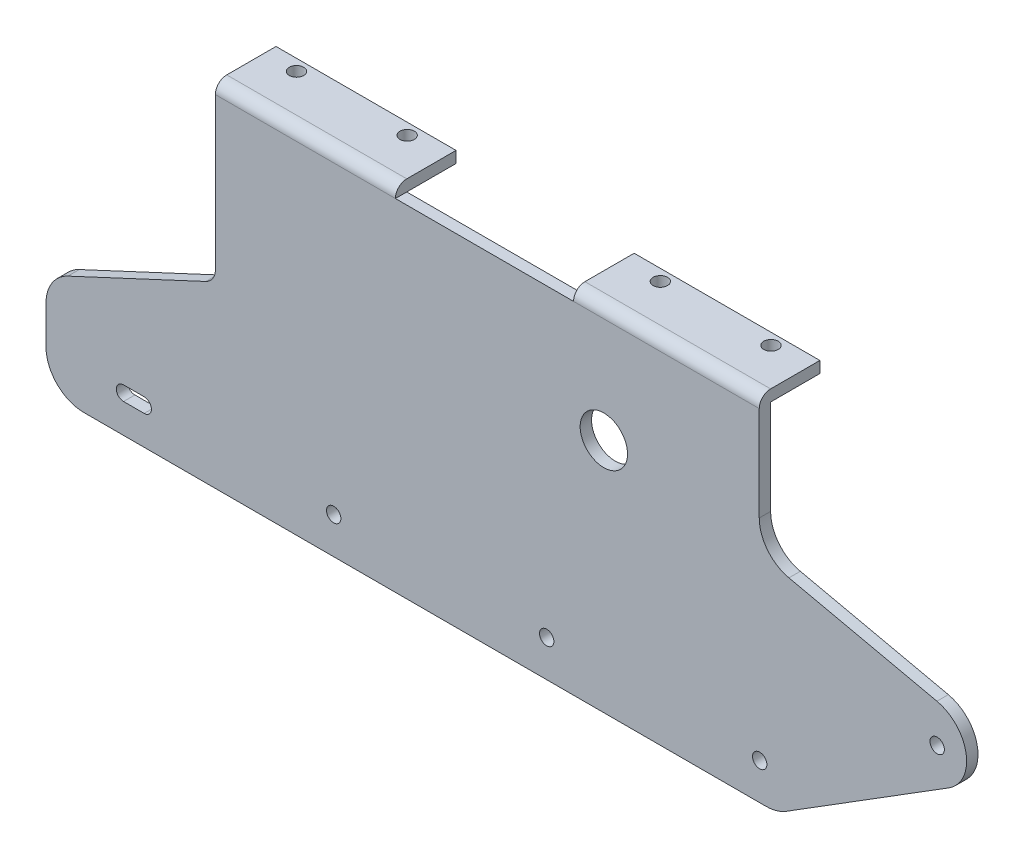
SolidWorks part; units mm, degrees
material "1060 Alloy"
ref_plane "Front Plane" through (0, 0, 0) normal (0, 0, 1) x (1, 0, 0)
ref_plane "Top Plane" through (0, 0, 0) normal (0, 1, 0) x (1, 0, 0)
ref_plane "Right Plane" through (0, 0, 0) normal (1, 0, 0) x (0, 0, -1)
sketch "Sketch1" plane through (0, 0, 0) normal (0, 0, 1) x (1, 0, 0)
  line L0 (0, 0) -> (143.5, 0)
  line L1 (143.5, 0) -> (143.5, -25)
  line L2 (151.3356, -34.763) -> (190.3874, -43.4205)
  line L3 (193.5222, -61.664) -> (150.6069, -88.4805)
  line L4 (145.3077, -90) -> (-34.6923, -90)
  line L5 (-44.6923, -80) -> (-44.6923, -70)
  line L6 (-38.9185, -60.9369) -> (-2.5276, -43.9676)
  line L7 (0, 0) -> (0, -40)
  arc A0 (-44.6923, -70) -> (-38.9185, -60.9369) centre (-34.6923, -70) cw
  arc A1 (143.5, -25) -> (151.3356, -34.763) centre (153.5, -25) ccw
  arc A2 (190.3874, -43.4205) -> (193.5222, -61.664) centre (188.223, -53.1835) cw
  arc A3 (145.3077, -90) -> (150.6069, -88.4805) centre (145.3077, -80) ccw
  arc A4 (-44.6923, -80) -> (-34.6923, -90) centre (-34.6923, -80) ccw
  arc A5 (-2.5276, -43.9676) -> (0, -40) centre (-4.3777, -40) ccw
  dimension "D6" = 10
  dimension "D7" = 10
  dimension "D10" = 10
  dimension "D11" = 40
  dimension "D12" = 10
  dimension "D15" = 10
  dimension "D1" = 143.5
  dimension "D2" = 25
  dimension "D3" = 40
  dimension "D4" = 90
  dimension "D5" = 12.5
  dimension "D8" = 180
  dimension "D9" = 32
  dimension "D13" = 10
  dimension "D14" = 25
extrude "Boss-Extrude1" add sketch "Sketch1" along normal blind 3
sketch "Sketch2" plane through (0, 0, 3) normal (0, 0, 1) x (1, 0, 0)
  line L0 (190.448, -53.5027) -> (198.218, -53.5027) construction
  line L1 (190.448, -53.5027) -> (190.3874, -43.4205) construction
  line L2 (190.448, -53.5027) -> (190.448, -63.585) construction
  line L3 (150.6069, -88.4805) -> (193.5222, -61.664) construction
  line L4 (143.6184, -80.35) -> (143.6184, -90) construction
  line L5 (-34.6923, -90) -> (145.3077, -90) construction
  line L6 (143.6184, -80.35) -> (163.6184, -80.35) construction
  line L7 (143.6184, -80.35) -> (87.4184, -80.35) construction
  line L8 (87.4184, -80.35) -> (31.2184, -80.35) construction
  line L9 (31.2184, -80.35) -> (-18.7816, -80.35) construction
  line L10 (-18.7816, -80.35) -> (-24.2316, -80.35) construction
  line L11 (-18.7816, -82.25) -> (-24.2316, -82.25)
  line L12 (-18.7816, -78.45) -> (-24.2316, -78.45)
  line L13 (102.5, -27.75) -> (0, -27.75) construction
  line L14 (0, 0) -> (0, -40) construction
  line L15 (143.5, 0) -> (0, 0) construction
  circle A0 centre (190.448, -53.5027) radius 1.9
  arc A1 (193.5222, -61.664) -> (190.3874, -43.4205) centre (188.223, -53.1835) ccw construction
  circle A2 centre (143.6184, -80.35) radius 1.9
  circle A3 centre (87.4184, -80.35) radius 1.9
  circle A4 centre (31.2184, -80.35) radius 1.9
  arc A5 (-18.7816, -82.25) -> (-18.7816, -78.45) centre (-18.7816, -80.35) ccw
  arc A6 (-24.2316, -78.45) -> (-24.2316, -82.25) centre (-24.2316, -80.35) ccw
  circle A7 centre (102.5, -27.75) radius 6.25
  point P22 (-21.5066, -80.35)
  dimension "D1" = 3.8
  dimension "D7" = 1.9
  dimension "D8" = 5.45
  dimension "D11" = 12.5
  dimension "D2" = 7.77
  dimension "D3" = 9.65
  dimension "D4" = 20
  dimension "D5" = 56.2
  dimension "D6" = 50
  dimension "D9" = 102.5
  dimension "D10" = 27.75
extrude "Cut-Extrude1" cut sketch "Sketch2" against normal through all contours A7 | A2 | A0 | A3 | A4 | L12 A6 L11 A5
sketch "Sketch3" plane through (143.5, 0, 0) normal (1, 0, 0) x (0, 0, -1)
  line L0 (0, 0) -> (13, 0)
  line L1 (0, 3) -> (13, 3)
  line L2 (13, 3) -> (13, 0)
  line L3 (-3, 0) -> (0, 0)
  line L4 (-3, -25) -> (-3, 0) construction
  line L5 (-3, -25) -> (-3, 0)
  line L6 (0, -25) -> (0, 0) construction
  line L7 (0, -25) -> (0, 0)
  arc A0 (0, 3) -> (-3, 0) centre (0, 0) ccw
  dimension "D1" = 3
  dimension "D2" = 16
extrude "Boss-Extrude2" add sketch "Sketch3" against normal up to surface (143.5 mm away) contours L0 L2 L1 A0 L3 up to face at (0, -20, 1.5)
sketch "Sketch4" plane through (0, 3, 0) normal (0, 1, 0) x (1, 0, 0)
  line L0 (47.5, 13) -> (47.5, -3)
  line L1 (0, 13) -> (143.5, 13) construction
  line L2 (143.5, -3) -> (0, -3) construction
  line L3 (47.5, -3) -> (94.5, -3)
  line L4 (94.5, -3) -> (94.5, 13)
  line L5 (94.5, 13) -> (47.5, 13)
  line L6 (0, 13) -> (0, 0) construction
  line L7 (143.5, 0) -> (143.5, 13) construction
  dimension "D1" = 47.5
  dimension "D2" = 49
extrude "Cut-Extrude2" cut sketch "Sketch4" against normal up to vertex (3 mm away) contours L5 L0 L3 L4 up to point (143.5, 0, 3)
sketch "Sketch5" plane through (0, 3, 0) normal (0, 1, 0) x (1, 0, 0)
  line L0 (0, 10) -> (143.5, 10) construction
  line L1 (0, 13) -> (0, 0) construction
  line L2 (143.5, 0) -> (143.5, 13) construction
  line L3 (0, 13) -> (47.5, 13) construction
  line L4 (47.5, 13) -> (47.5, 0) construction
  line L5 (94.5, 0) -> (94.5, 13) construction
  circle A0 centre (8.4, 10) radius 1.9
  circle A1 centre (37.6, 10) radius 1.9
  circle A2 centre (104.4, 10) radius 1.9
  circle A3 centre (133.6, 10) radius 1.9
  dimension "D2" = 3.8
  dimension "D1" = 3
  dimension "D3" = 8.4
  dimension "D4" = 9.9
  dimension "D5" = 9.9
  dimension "D6" = 9.9
extrude "Cut-Extrude3" cut sketch "Sketch5" against normal through all contours A0 | A1 | A2 | A3
